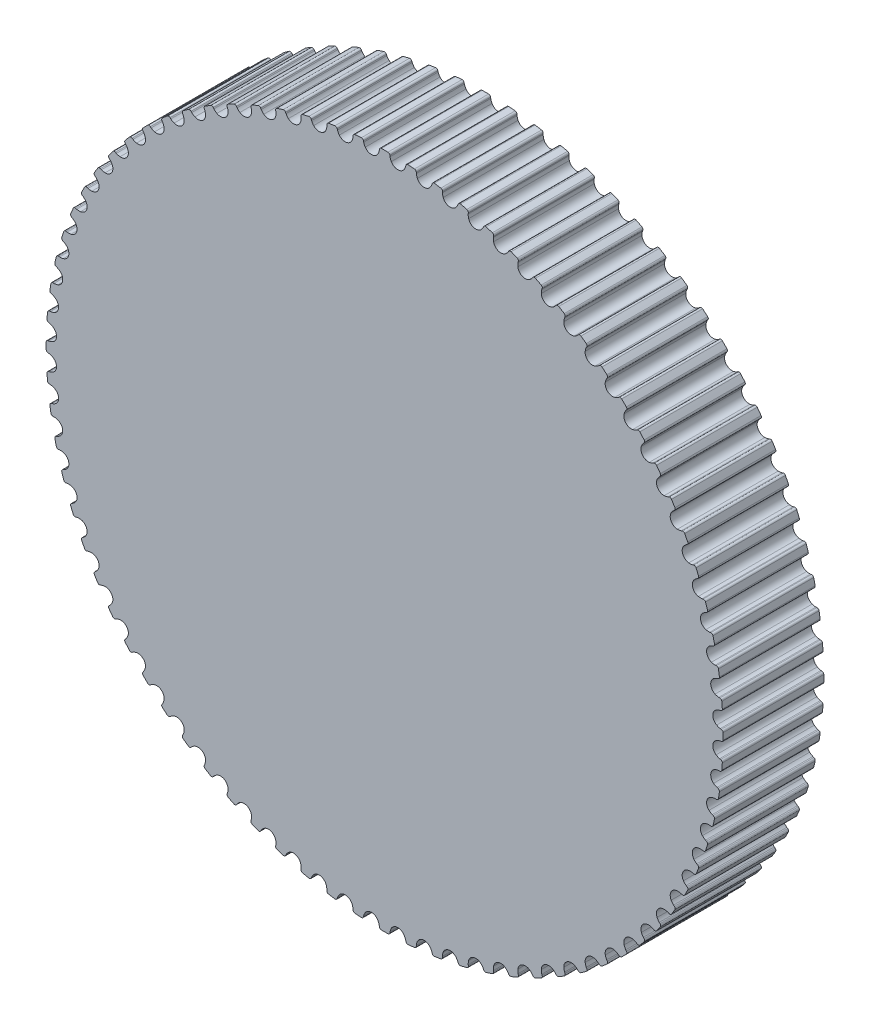
SolidWorks part; units mm, degrees
note: '?' marks a value the reader was unsure of.
ref_plane "Front Plane" through (0, 0, 0) normal (0, 0, 1) x (1, 0, 0)
ref_plane "Top Plane" through (0, 0, 0) normal (0, 1, 0) x (1, 0, 0)
ref_plane "Right Plane" through (0, 0, 0) normal (1, 0, 0) x (0, 0, -1)
sketch "Sketch1" plane through (0, 0, 0) normal (0, 0, 1) x (1, 0, 0)
  line L0 (0, 0) -> (0, 25.4648) construction
  line L1 (0, 0) -> (0.9997, 25.4452) construction
  line L2 (0, 0) -> (1.3993, 25.4263) construction
  circle A0 centre (0, 0) radius 25.4648 construction
  circle A1 centre (0, 0) radius 24.4608 construction
  circle A2 centre (0, 0) radius 25.2108 construction
  arc A3 (0.9603, 24.4419) -> (0.4969, 24.727) centre (0.9821, 24.9965) cw
  arc A4 (0.401, 24.9965) -> (0.3902, 25.0744) centre (1.3853, 25.1727) cw
  circle A5 centre (0, 0) radius 25.0608 construction
  arc A6 (-0.2424, 25.2096) -> (0.2424, 25.2096) centre (0, 0) cw
  arc A7 (0.2424, 25.2096) -> (0.3902, 25.0744) centre (0.2409, 25.0596) cw
  arc A8 (0.401, 24.9965) -> (0.4969, 24.727) centre (1.2585, 25.15) ccw
  arc A9 (-0.9603, 24.4419) -> (-0.4969, 24.727) centre (-0.9821, 24.9965) ccw
  arc A10 (-0.401, 24.9965) -> (-0.4969, 24.727) centre (-1.2585, 25.15) cw
  arc A11 (-0.401, 24.9965) -> (-0.3902, 25.0744) centre (-1.3853, 25.1727) ccw
  arc A12 (-0.2424, 25.2096) -> (-0.3902, 25.0744) centre (-0.2409, 25.0596) ccw
  arc A13 (-0.9603, 24.4419) -> (0.9603, 24.4419) centre (0, 0) cw
  dimension "D1" = 50.9296
  dimension "D6" = 0.555
  dimension "D7" = 1
  dimension "D9" = 0.15
  dimension "D2" = 2.25
  dimension "D3" = 0.9
  dimension "D4" = 1.004
  dimension "D5" = 0.75
  dimension "D8" = 0.15
extrude "Boss-Extrude1" add sketch "Sketch1" along normal blind 7.5
ref_axis "Axis1" through (0, 0, -0.375) along (0, 0, 1)?
pattern_circular "CirPattern1" count 80 over 360 about axis through (0, 0, 0) along (0, 0, 1) of "Boss-Extrude1"
sketch "Sketch2" plane through (0, 0, 0) normal (0, 0, -1) x (-1, 0, 0)
  circle A0 centre (0, 0) radius 24.4608
  arc A1 (0.9603, 24.4419) -> (-0.9603, 24.4419) centre (0, 0) ccw construction
extrude "Boss-Extrude2" add sketch "Sketch2" against normal up to surface (7.5 mm away)
equation "\"NumTeeth\"= 80'The number of teeth that the pulley has"
equation "\"ToothPitch\"= 2.00mm'Distance between 2 teeth"
equation "\"PulleyDia\"= \"NumTeeth\" * \"ToothPitch\" / PI"
equation "\"ToothAng\"= ( 360deg / \"NumTeeth\" ) * 1deg"
equation "\"TransOffsetAngle\"= \"ToothAng\" * .2deg"
equation "\"ShoulderRad\"= 0.15mm"
equation "\"RootRad\"= 0.555mm"
equation "\"TransRad\"= 1mm"
equation "\"ToothHeight\"= 0.75mm"
equation "\"PLD\"= 0.254mm"
equation "\"D1@CirPattern1\"=\"NumTeeth\""
equation "\"D1@Sketch1\"=\"PulleyDia\""
equation "\"D7@Sketch1\"=\"TransRad\""
equation "\"D9@Sketch1\"=\"ShoulderRad\""
equation "\"D6@Sketch1\"=\"RootRad\""
equation "\"D3@Sketch1\"=\"TransOffsetAngle\""
equation "\"D5@Sketch1\"=\"ToothHeight\""
equation "\"D2@Sketch1\"=\"ToothAng\"/2"
equation "\"D4@Sketch1\"=\"PLD\"+\"ToothHeight\""
equation "\"D8@Sketch1\"=\"ShoulderRad\""
